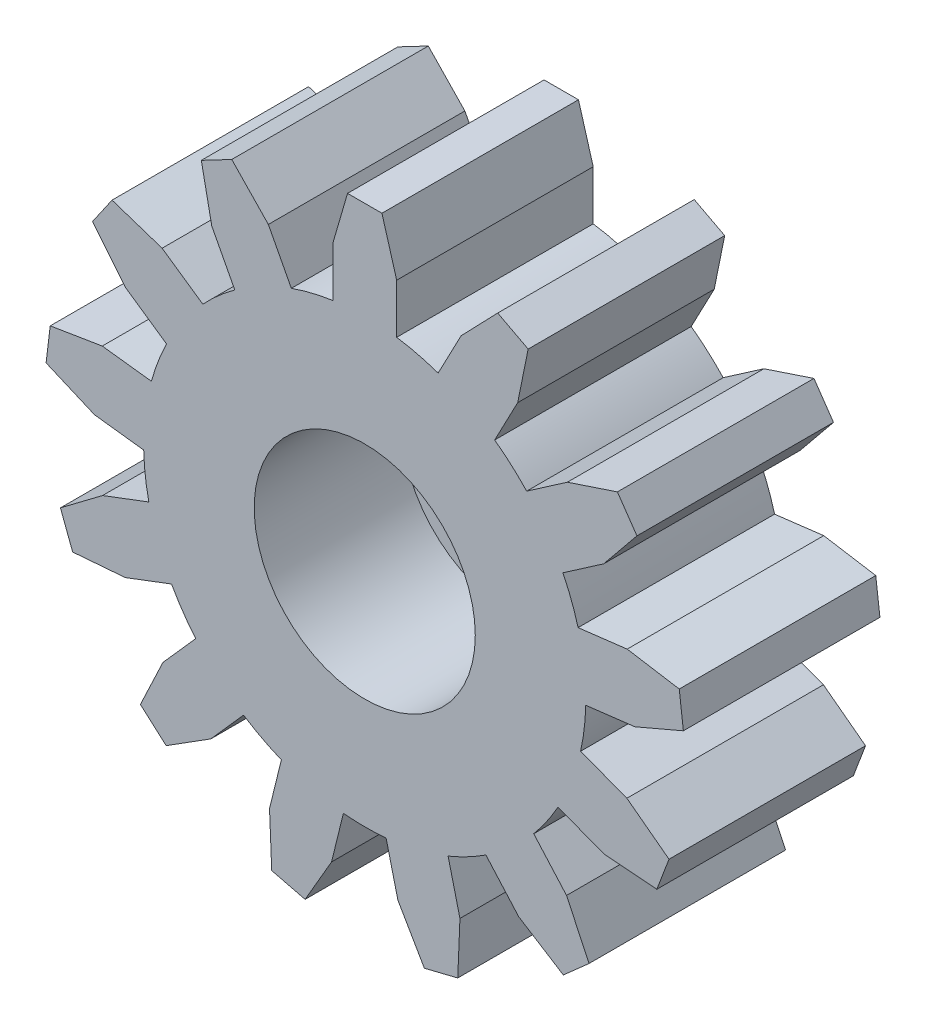
SolidWorks part; units mm, degrees
ref_plane "Płaszczyzna przednia" through (0, 0, 0) normal (0, 0, 1) x (1, 0, 0)
ref_plane "Płaszczyzna górna" through (0, 0, 0) normal (0, 1, 0) x (1, 0, 0)
ref_plane "Płaszczyzna prawa" through (0, 0, 0) normal (1, 0, 0) x (0, 0, -1)
sketch "Szkic1" plane through (0, 0, 0) normal (0, 0, 1) x (1, 0, 0)
  line L0 (-0.65, 5.4601) -> (-0.65, 4.4528)
  line L2 (0.65, 4.4528) -> (0.65, 5.4601)
  line L4 (-0.65, 5.4601) -> (-0.35, 6.4906)
  line L5 (0.65, 5.4601) -> (0.35, 6.4906)
  line L6 (-0.35, 6.4906) -> (0.35, 6.4906)
  line L7 (1.9619, 5.1368) -> (1.4938, 4.2448)
  line L8 (1.9619, 5.1368) -> (2.7064, 5.9098)
  line L9 (2.7064, 5.9098) -> (3.3262, 5.5845)
  line L10 (3.113, 4.5326) -> (3.3262, 5.5845)
  line L11 (2.6449, 3.6407) -> (3.113, 4.5326)
  line L12 (4.1243, 3.6366) -> (3.2953, 3.0644)
  line L13 (4.1243, 3.6366) -> (5.1428, 3.9751)
  line L14 (5.1428, 3.9751) -> (5.5405, 3.399)
  line L15 (4.8628, 2.5668) -> (5.5405, 3.399)
  line L16 (4.0338, 1.9945) -> (4.8628, 2.5668)
  line L17 (5.342, 1.3034) -> (4.342, 1.182)
  line L18 (5.342, 1.3034) -> (6.4011, 1.1298)
  line L19 (6.4011, 1.1298) -> (6.4854, 0.4349)
  line L20 (5.4987, 0.0129) -> (6.4854, 0.4349)
  line L21 (4.4987, -0.1085) -> (5.4987, 0.0129)
  line L22 (5.3358, -1.3284) -> (4.3939, -0.9712)
  line L23 (5.3358, -1.3284) -> (6.1929, -1.9743)
  line L24 (6.1929, -1.9743) -> (5.9447, -2.6288)
  line L25 (4.8748, -2.5439) -> (5.9447, -2.6288)
  line L26 (3.933, -2.1867) -> (4.8748, -2.5439)
  line L27 (4.1073, -3.6559) -> (3.4393, -2.9019)
  line L28 (4.1073, -3.6559) -> (4.566, -4.6262)
  line L29 (4.566, -4.6262) -> (4.0421, -5.0904)
  line L30 (3.1342, -4.518) -> (4.0421, -5.0904)
  line L31 (2.4662, -3.764) -> (3.1342, -4.518)
  line L32 (1.9378, -5.1459) -> (1.6967, -4.1679)
  line L33 (1.9378, -5.1459) -> (1.8931, -6.2182)
  line L34 (1.8931, -6.2182) -> (1.2135, -6.3857)
  line L35 (0.6756, -5.457) -> (1.2135, -6.3857)
  line L36 (0.4345, -4.479) -> (0.6756, -5.457)
  line L37 (-0.6756, -5.457) -> (-0.4345, -4.479)
  line L38 (-0.6756, -5.457) -> (-1.2135, -6.3857)
  line L39 (-1.2135, -6.3857) -> (-1.8931, -6.2182)
  line L40 (-1.9378, -5.1459) -> (-1.8931, -6.2182)
  line L41 (-1.6967, -4.1679) -> (-1.9378, -5.1459)
  line L42 (-3.1342, -4.518) -> (-2.4662, -3.764)
  line L43 (-3.1342, -4.518) -> (-4.0421, -5.0904)
  line L44 (-4.0421, -5.0904) -> (-4.566, -4.6262)
  line L45 (-4.1073, -3.6559) -> (-4.566, -4.6262)
  line L46 (-3.4393, -2.9019) -> (-4.1073, -3.6559)
  line L47 (-4.8748, -2.5439) -> (-3.933, -2.1867)
  line L48 (-4.8748, -2.5439) -> (-5.9447, -2.6288)
  line L49 (-5.9447, -2.6288) -> (-6.1929, -1.9743)
  line L50 (-5.3358, -1.3284) -> (-6.1929, -1.9743)
  line L51 (-4.3939, -0.9712) -> (-5.3358, -1.3284)
  line L52 (-5.4987, 0.0129) -> (-4.4987, -0.1085)
  line L53 (-5.4987, 0.0129) -> (-6.4854, 0.4349)
  line L54 (-6.4854, 0.4349) -> (-6.4011, 1.1298)
  line L55 (-5.342, 1.3034) -> (-6.4011, 1.1298)
  line L56 (-4.342, 1.182) -> (-5.342, 1.3034)
  line L57 (-4.8628, 2.5668) -> (-4.0338, 1.9945)
  line L58 (-4.8628, 2.5668) -> (-5.5405, 3.399)
  line L59 (-5.5405, 3.399) -> (-5.1428, 3.9751)
  line L60 (-4.1243, 3.6366) -> (-5.1428, 3.9751)
  line L61 (-3.2953, 3.0644) -> (-4.1243, 3.6366)
  line L62 (-3.113, 4.5326) -> (-2.6449, 3.6407)
  line L63 (-3.113, 4.5326) -> (-3.3262, 5.5845)
  line L64 (-3.3262, 5.5845) -> (-2.7064, 5.9098)
  line L65 (-1.9619, 5.1368) -> (-2.7064, 5.9098)
  line L66 (-1.4938, 4.2448) -> (-1.9619, 5.1368)
  arc A1 (-0.65, 4.4528) -> (-1.4938, 4.2448) centre (0, 0) ccw
  arc A3 (-2.6449, 3.6407) -> (-3.2953, 3.0644) centre (0, 0) ccw
  arc A4 (-4.0338, 1.9945) -> (-4.342, 1.182) centre (0, 0) ccw
  arc A5 (-4.4987, -0.1085) -> (-4.3939, -0.9712) centre (0, 0) ccw
  arc A6 (-3.933, -2.1867) -> (-3.4393, -2.9019) centre (0, 0) ccw
  arc A7 (-2.4662, -3.764) -> (-1.6967, -4.1679) centre (0, 0) ccw
  arc A8 (-0.4345, -4.479) -> (0.4345, -4.479) centre (0, 0) ccw
  arc A9 (1.6967, -4.1679) -> (2.4662, -3.764) centre (0, 0) ccw
  arc A10 (3.4393, -2.9019) -> (3.933, -2.1867) centre (0, 0) ccw
  arc A11 (4.3939, -0.9712) -> (4.4987, -0.1085) centre (0, 0) ccw
  arc A12 (4.342, 1.182) -> (4.0338, 1.9945) centre (0, 0) ccw
  arc A13 (3.2953, 3.0644) -> (2.6449, 3.6407) centre (0, 0) ccw
  arc A14 (1.4938, 4.2448) -> (0.65, 4.4528) centre (0, 0) ccw
  circle A15 centre (0, 0) radius 2.25
  circle A16 centre (0, 0) radius 1
  point P82 (0, 0)
  dimension "D1" = 13
  dimension "D2" = 1.3
  dimension "D3" = 4.5
  dimension "D4" = 2
extrude "Dodanie-wyciągnięcie1" add sketch "Szkic1" along normal blind 4 contours L7 A14 L2 L5 L6 L4 L0 A1 L66 L65 L64 L63 L62 A3 L61 L60 L59 L58 L57 A4 L56 L55 L54 L53 L52 A5 L51 L50 L49 L48 L47 A6 L46 L45 L44 L43 L42 A7 L41 L40 L39 L38 L37 A8 L36 L35 L34 L33 L32 A9 L31 region at (-0.3245, 5.9243, 0)
extrude "Dodanie-wyciągnięcie2" add sketch "Szkic1<3>" along normal blind 1 contours A15 A16 region at (-2.1864, 0, 0)
sketch "Szkic1<3>" plane through (0, 0, 0) normal (0, 0, 1) x (1, 0, 0) same geometry as "Szkic1"
